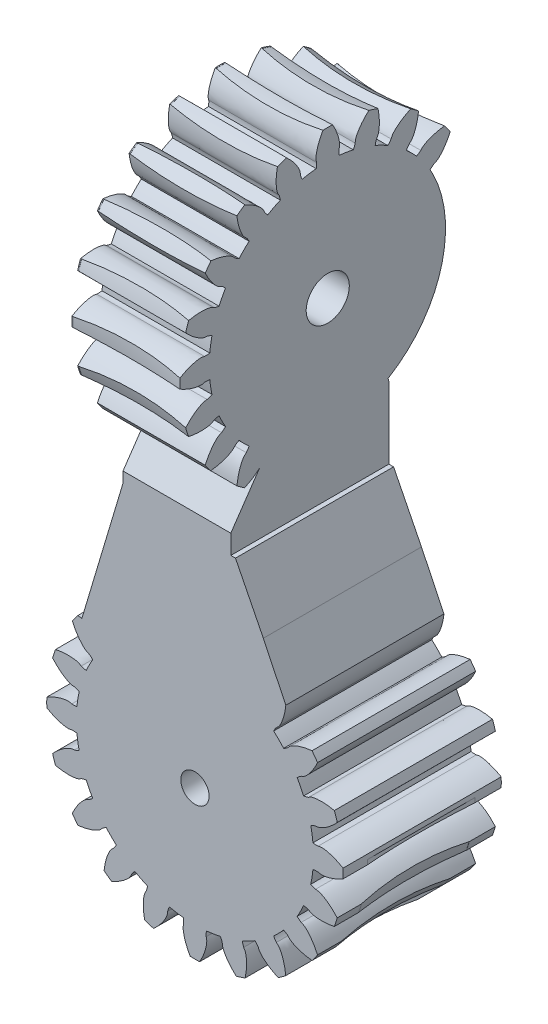
SolidWorks part; units mm, degrees
ref_plane "Спереди" through (0, 0, 0) normal (0, 0, 1) x (1, 0, 0)
ref_plane "Сверху" through (0, 0, 0) normal (0, 1, 0) x (1, 0, 0)
ref_plane "Справа" through (0, 0, 0) normal (1, 0, 0) x (0, 0, -1)
sketch "Sketch1" plane through (0, 0, 0) normal (0, 1, 0) x (1, 0, 0)
  line L1 (0, 0) -> (39.7576, 0)
  line L2 (0, 0) -> (0, 13.7359)
  line L3 (0, 13.7359) -> (39.7576, 13.7359)
  line L4 (39.7576, 0) -> (39.7576, 13.7359)
extrude "Boss-Extrude1" add sketch "Sketch1" along normal blind 49
sketch "Sketch2" plane through (0, 0, 0) normal (0, 0, 1) x (1, 0, 0)
  circle A0 centre (21.6386, 13.5388) radius 1.05
  dimension "D1" = 2.1
extrude "Cut-Extrude1" cut sketch "Sketch2" against normal blind 20
sketch "Sketch3" plane through (0, 0, 0) normal (0, 0, 1) x (1, 0, 0)
  line L0 (0, 49) -> (0, 0) construction
  line L1 (0, 49) -> (16.2999, 49)
  line L2 (0, 49) -> (0, 30.465)
  line L3 (0, 30.465) -> (16.2999, 30.465)
  line L4 (16.2999, 49) -> (16.2999, 30.465)
  line L5 (39.7576, 49) -> (39.7576, 0) construction
  line L6 (39.7576, 49) -> (24.2999, 49)
  line L7 (39.7576, 49) -> (39.7576, 29.8211)
  line L8 (39.7576, 29.8211) -> (24.2999, 29.8211)
  line L9 (24.2999, 49) -> (24.2999, 29.8211)
  dimension "D1" = 8
extrude "Cut-Extrude2" cut sketch "Sketch3" against normal blind 20
sketch "Sketch4" plane through (24.2999, 0, 0) normal (1, 0, 0) x (0, 0, -1)
  circle A0 centre (9.1973, 42.7526) radius 1.6
  dimension "D1" = 3.2
extrude "Cut-Extrude3" cut sketch "Sketch4" against normal blind 10
sketch "Sketch5" plane through (0, 0, 0) normal (0, 0, 1) x (1, 0, 0)
  line L0 (30.5736, 18.0296) -> (24.6471, 29.8211)
  line L1 (43.1167, 38.1094) -> (43.1167, -6.2044)
  line L2 (43.1167, -6.2044) -> (-5.9864, -7.089)
  line L3 (-5.9864, -7.089) -> (-3.1631, 36.0058)
  line L4 (16.2999, 30.465) -> (12.3499, 17.2429)
  line L5 (24.2999, 29.8211) -> (39.7576, 29.8211) construction
  line L6 (24.6471, 29.8211) -> (43.1167, 38.1094)
  line L7 (16.2999, 30.465) -> (-3.1631, 36.0058)
  circle A0 centre (21.6386, 13.5388) radius 10
  line M4 (16.2999, 30.465) -> (0, 30.465)
  line M5 (0, 30.465) -> (0, 0)
  line M6 (0, 0) -> (39.7576, 0)
  line M7 (39.7576, 0) -> (39.7576, 29.8211)
  line M8 (39.7576, 29.8211) -> (24.2999, 29.8211)
  dimension "D1" = 20
extrude "Cut-Extrude4" cut sketch "Sketch5" against normal blind 23 contours A0 L7 M4 M5 M6 M7 M8 region at (28.0579, 24.1503, 0)
sketch "Sketch6" plane through (16.2999, 0, 0) normal (-1, 0, 0) x (0, 0, 1)
  line L0 (-9.1973, 50.2582) -> (3.3847, 50.2582)
  line L1 (3.3847, 50.2582) -> (3.3847, 37.4424)
  line L2 (-5.429, 36.2614) -> (1.4031, 26.2756)
  line L3 (1.4031, 26.2756) -> (3.3847, 37.4424)
  circle A0 centre (-9.1973, 42.7526) radius 7.5056
  line M2 (-13.7359, 30.465) -> (0, 30.465)
  line M3 (0, 30.465) -> (0, 49)
  line M4 (0, 49) -> (-13.7359, 49)
extrude "Cut-Extrude5" cut sketch "Sketch6" against normal blind 28 and the other way blind 10 contours A0 L2 L3 L1 L0 M4 M3 M2 | A0 L2 M2 M3 M4 region at (16.2999, 40.6436, 1.0177) region at (16.2999, 39.3835, -1.6823)
sketch "Sketch7" plane through (16.2999, 0, 0) normal (-1, 0, 0) x (0, 0, 1)
  circle A0 centre (-9.1973, 42.7545) radius 3
  arc A1 (-8.3632, 51.8961) -> (-8.3414, 51.5128) centre (-6.7958, 51.7931) ccw
  arc A2 (-8.8499, 53.749) -> (-9.5447, 53.749) centre (-9.1973, 42.7564) ccw
  arc A3 (-10.0532, 51.5128) -> (-10.0313, 51.8961) centre (-11.5987, 51.7931) ccw
  arc A4 (-10.0532, 51.5128) -> (-11.0898, 51.3486) centre (-9.1973, 42.7545) ccw
  arc A5 (-11.229, 51.7064) -> (-11.0898, 51.3486) centre (-9.7064, 52.0928) ccw
  arc A6 (-12.2644, 53.3182) -> (-12.9252, 53.1036) centre (-9.1973, 42.7545) ccw
  arc A7 (-12.7177, 50.8196) -> (-12.8154, 51.1909) centre (-14.2743, 50.6086) ccw
  arc A8 (-12.7177, 50.8196) -> (-13.6529, 50.3432) centre (-9.1973, 42.7545) ccw
  arc A9 (-13.8958, 50.6404) -> (-13.6529, 50.3432) centre (-12.5672, 51.4784) ccw
  arc A10 (-15.3787, 51.8534) -> (-15.9407, 51.4451) centre (-9.1973, 42.7545) ccw
  arc A11 (-15.0377, 49.337) -> (-15.2453, 49.6599) centre (-16.4528, 48.6553) ccw
  arc A12 (-15.0377, 49.337) -> (-15.7798, 48.5949) centre (-9.1973, 42.7545) ccw
  arc A13 (-16.1027, 48.8025) -> (-15.7798, 48.5949) centre (-15.0981, 50.0101) ccw
  arc A14 (-17.8878, 49.4979) -> (-18.2962, 48.9359) centre (-9.1973, 42.7545) ccw
  arc A15 (-16.786, 47.2101) -> (-17.0832, 47.453) centre (-17.9212, 46.1244) ccw
  arc A16 (-16.786, 47.2101) -> (-17.2624, 46.2749) centre (-9.1973, 42.7545) ccw
  arc A17 (-17.6337, 46.3726) -> (-17.2624, 46.2749) centre (-17.0514, 47.8315) ccw
  arc A18 (-19.5463, 46.4824) -> (-19.761, 45.8216) centre (-9.1973, 42.7545) ccw
  arc A19 (-17.7914, 44.647) -> (-18.1492, 44.7862) centre (-18.5356, 43.2637) ccw
  arc A20 (-17.7914, 44.647) -> (-17.9556, 43.6104) centre (-9.1973, 42.7545) ccw
  arc A21 (-18.3389, 43.5885) -> (-17.9556, 43.6104) centre (-18.2359, 45.156) ccw
  arc A22 (-20.1918, 43.1019) -> (-20.1918, 42.4071) centre (-9.1973, 42.7545) ccw
  arc A23 (-17.9556, 41.8986) -> (-18.3389, 41.9205) centre (-18.2359, 40.353) ccw
  arc A24 (-17.9556, 41.8986) -> (-17.7914, 40.862) centre (-9.1973, 42.7545) ccw
  arc A25 (-18.1492, 40.7228) -> (-17.7914, 40.862) centre (-18.5356, 42.2453) ccw
  arc A26 (-19.761, 39.6874) -> (-19.5463, 39.0266) centre (-9.1973, 42.7545) ccw
  arc A27 (-17.2624, 39.2341) -> (-17.6337, 39.1364) centre (-17.0514, 37.6775) ccw
  arc A28 (-17.2624, 39.2341) -> (-16.786, 38.2989) centre (-9.1973, 42.7545) ccw
  arc A29 (-17.0832, 38.056) -> (-16.786, 38.2989) centre (-17.9212, 39.3846) ccw
  arc A30 (-18.2962, 36.5731) -> (-17.8878, 36.011) centre (-9.1973, 42.7545) ccw
  arc A31 (-15.7798, 36.9141) -> (-16.1027, 36.7065) centre (-15.0981, 35.4989) ccw
  arc A32 (-15.7798, 36.9141) -> (-15.0377, 36.172) centre (-9.1973, 42.7545) ccw
  arc A33 (-15.2453, 35.849) -> (-15.0377, 36.172) centre (-16.4528, 36.8537) ccw
  arc A34 (-15.9407, 34.0639) -> (-15.3787, 33.6556) centre (-9.1973, 42.7545) ccw
  arc A35 (-13.6529, 35.1658) -> (-13.8958, 34.8686) centre (-12.5672, 34.0306) ccw
  arc A36 (-13.6529, 35.1658) -> (-12.7177, 34.6894) centre (-9.1973, 42.7545) ccw
  arc A37 (-12.8154, 34.3181) -> (-12.7177, 34.6894) centre (-14.2743, 34.9004) ccw
  arc A38 (-12.9252, 32.4054) -> (-12.2644, 32.1907) centre (-9.1973, 42.7545) ccw
  arc A39 (-11.0898, 34.1604) -> (-11.229, 33.8026) centre (-9.7064, 33.4162) ccw
  arc A40 (-11.0898, 34.1604) -> (-10.0532, 33.9962) centre (-9.1973, 42.7545) ccw
  arc A41 (-10.0313, 33.6129) -> (-10.0532, 33.9962) centre (-11.5987, 33.7159) ccw
  arc A42 (-9.5447, 31.76) -> (-8.8499, 31.76) centre (-9.1973, 42.7526) ccw
  arc A43 (-8.3414, 33.9962) -> (-8.3632, 33.6129) centre (-6.7958, 33.7159) ccw
  arc A44 (-8.3414, 33.9962) -> (-7.3048, 34.1604) centre (-9.1973, 42.7545) ccw
  arc A45 (-7.1656, 33.8026) -> (-7.3048, 34.1604) centre (-8.6881, 33.4162) ccw
  arc A46 (-6.1302, 32.1907) -> (-5.4694, 32.4054) centre (-9.1973, 42.7545) ccw
  arc A47 (-5.6768, 34.6894) -> (-5.5792, 34.3181) centre (-4.1203, 34.9004) ccw
  arc A48 (-5.6768, 34.6894) -> (-4.7417, 35.1658) centre (-9.1973, 42.7545) ccw
  arc A49 (-4.4988, 34.8686) -> (-4.7417, 35.1658) centre (-5.8274, 34.0306) ccw
  arc A50 (-3.0159, 33.6556) -> (-2.4538, 34.0639) centre (-9.1973, 42.7545) ccw
  arc A51 (-3.3569, 36.172) -> (-3.1492, 35.849) centre (-1.9417, 36.8537) ccw
  arc A52 (-3.3569, 36.172) -> (-2.6148, 36.9141) centre (-9.1973, 42.7545) ccw
  arc A53 (-2.2918, 36.7065) -> (-2.6148, 36.9141) centre (-3.2965, 35.4989) ccw
  arc A54 (-0.5067, 36.011) -> (-0.0983, 36.5731) centre (-9.1973, 42.7545) ccw
  arc A55 (-1.6086, 38.2989) -> (-1.3114, 38.056) centre (-0.4734, 39.3846) ccw
  arc A56 (-1.6086, 38.2989) -> (-1.1321, 39.2341) centre (-9.1973, 42.7545) ccw
  arc A57 (-0.7609, 39.1364) -> (-1.1321, 39.2341) centre (-1.3432, 37.6775) ccw
  arc A58 (1.1518, 39.0266) -> (1.3665, 39.6874) centre (-9.1973, 42.7545) ccw
  arc A59 (-0.6032, 40.862) -> (-0.2454, 40.7228) centre (0.141, 42.2453) ccw
  arc A60 (-0.6032, 40.862) -> (-0.439, 41.8986) centre (-9.1973, 42.7545) ccw
  arc A61 (-0.0557, 41.9205) -> (-0.439, 41.8986) centre (-0.1587, 40.353) ccw
  arc A62 (1.7972, 42.4071) -> (1.7972, 43.1019) centre (-9.1973, 42.7545) ccw
  arc A63 (-0.439, 43.6104) -> (-0.0557, 43.5885) centre (-0.1587, 45.156) ccw
  arc A64 (-0.439, 43.6104) -> (-0.6032, 44.647) centre (-9.1973, 42.7545) ccw
  arc A65 (-0.2454, 44.7862) -> (-0.6032, 44.647) centre (0.141, 43.2637) ccw
  arc A66 (1.3665, 45.8216) -> (1.1518, 46.4824) centre (-9.1973, 42.7545) ccw
  arc A67 (-1.1321, 46.2749) -> (-0.7609, 46.3726) centre (-1.3432, 47.8315) ccw
  arc A68 (-1.1321, 46.2749) -> (-1.6086, 47.2101) centre (-9.1973, 42.7545) ccw
  arc A69 (-1.3114, 47.453) -> (-1.6086, 47.2101) centre (-0.4734, 46.1244) ccw
  arc A70 (-0.0983, 48.9359) -> (-0.5067, 49.4979) centre (-9.1973, 42.7545) ccw
  arc A71 (-2.6148, 48.5949) -> (-2.2918, 48.8025) centre (-3.2965, 50.0101) ccw
  arc A72 (-2.6148, 48.5949) -> (-3.3569, 49.337) centre (-9.1973, 42.7545) ccw
  arc A73 (-3.1492, 49.6599) -> (-3.3569, 49.337) centre (-1.9417, 48.6553) ccw
  arc A74 (-2.4538, 51.4451) -> (-3.0159, 51.8534) centre (-9.1973, 42.7545) ccw
  arc A75 (-4.7417, 50.3432) -> (-4.4988, 50.6404) centre (-5.8274, 51.4784) ccw
  arc A76 (-4.7417, 50.3432) -> (-5.6768, 50.8196) centre (-9.1973, 42.7545) ccw
  arc A77 (-5.5792, 51.1909) -> (-5.6768, 50.8196) centre (-4.1203, 50.6086) ccw
  arc A78 (-5.4694, 53.1036) -> (-6.1302, 53.3182) centre (-9.1973, 42.7545) ccw
  arc A79 (-7.3048, 51.3486) -> (-7.1656, 51.7064) centre (-8.6881, 52.0928) ccw
  arc A80 (-7.3048, 51.3486) -> (-8.3414, 51.5128) centre (-9.1973, 42.7545) ccw
  spline S0 degree 3 poles (-8.3632, 51.8961) (-8.3353, 51.9983) (-8.3222, 52.0737) (-8.3186, 52.1413) (-8.3185, 52.1775) (-8.321, 52.253) (-8.334, 52.3811) (-8.3676, 52.5694) (-8.4293, 52.8074) (-8.5268, 53.0907) (-8.6488, 53.3717) (-8.7612, 53.5917) (-8.8273, 53.7097) (-8.8499, 53.749) knots -0.544106 -0.544106 -0.544106 -0.544106 -0.367071 -0.332661 -0.285394 -0.214472 0.006914 0.350598 0.831726 1.464429 2.260634 2.903028 3.224225 3.224225 3.224225 3.224225 weights 1 1 1 1 1 1 1 1 1 1 1 1 1 1
  spline S1 degree 3 poles (-9.5447, 53.749) (-9.5673, 53.7097) (-9.6333, 53.5917) (-9.7458, 53.3717) (-9.8677, 53.0907) (-9.9652, 52.8074) (-10.027, 52.5694) (-10.0605, 52.3811) (-10.0736, 52.253) (-10.0761, 52.1775) (-10.076, 52.1413) (-10.0724, 52.0737) (-10.0593, 51.9983) (-10.0313, 51.8961) knots 0 0 0 0 0.321197 0.963591 1.759796 2.3925 2.873627 3.217311 3.438697 3.509619 3.556886 3.591297 3.768331 3.768331 3.768331 3.768331 weights 1 1 1 1 1 1 1 1 1 1 1 1 1 1
  spline S2 degree 3 poles (-11.229, 51.7064) (-11.234, 51.8122) (-11.2448, 51.888) (-11.2623, 51.9534) (-11.2734, 51.9878) (-11.2991, 52.0589) (-11.3511, 52.1767) (-11.4411, 52.3454) (-11.5735, 52.5527) (-11.7537, 52.792) (-11.9566, 53.0215) (-12.1315, 53.196) (-12.2307, 53.2879) (-12.2644, 53.3182) knots -0.544106 -0.544106 -0.544106 -0.544106 -0.367071 -0.332661 -0.285394 -0.214472 0.006914 0.350598 0.831726 1.464429 2.260634 2.903028 3.224225 3.224225 3.224225 3.224225 weights 1 1 1 1 1 1 1 1 1 1 1 1 1 1
  spline S3 degree 3 poles (-12.9252, 53.1036) (-12.9345, 53.0592) (-12.9609, 52.9266) (-12.9998, 52.6826) (-13.029, 52.3777) (-13.0342, 52.0781) (-13.0194, 51.8326) (-12.9931, 51.6432) (-12.9659, 51.5173) (-12.9449, 51.4447) (-12.9337, 51.4103) (-12.9093, 51.3472) (-12.8736, 51.2795) (-12.8154, 51.1909) knots 0 0 0 0 0.321197 0.963591 1.759796 2.3925 2.873627 3.217311 3.438697 3.509619 3.556886 3.591297 3.768331 3.768331 3.768331 3.768331 weights 1 1 1 1 1 1 1 1 1 1 1 1 1 1
  spline S4 degree 3 poles (-13.8958, 50.6404) (-13.9333, 50.7395) (-13.967, 50.8082) (-14.0038, 50.8651) (-14.025, 50.8944) (-14.0714, 50.954) (-14.1573, 51.05) (-14.2951, 51.1826) (-14.485, 51.3389) (-14.7304, 51.5108) (-14.9942, 51.6664) (-15.2145, 51.7783) (-15.3373, 51.8349) (-15.3787, 51.8534) knots -0.544106 -0.544106 -0.544106 -0.544106 -0.367071 -0.332661 -0.285394 -0.214472 0.006914 0.350598 0.831726 1.464429 2.260634 2.903028 3.224225 3.224225 3.224225 3.224225 weights 1 1 1 1 1 1 1 1 1 1 1 1 1 1
  spline S5 degree 3 poles (-15.9407, 51.4451) (-15.9359, 51.4) (-15.92, 51.2657) (-15.8816, 51.0216) (-15.8152, 50.7226) (-15.7275, 50.4361) (-15.6376, 50.2072) (-15.554, 50.0352) (-15.4893, 49.9239) (-15.4469, 49.8613) (-15.4256, 49.8321) (-15.3829, 49.7795) (-15.328, 49.7262) (-15.2453, 49.6599) knots 0 0 0 0 0.321197 0.963591 1.759796 2.3925 2.873627 3.217311 3.438697 3.509619 3.556886 3.591297 3.768331 3.768331 3.768331 3.768331 weights 1 1 1 1 1 1 1 1 1 1 1 1 1 1
  spline S6 degree 3 poles (-16.1027, 48.8025) (-16.169, 48.8852) (-16.2223, 48.9401) (-16.2749, 48.9828) (-16.3041, 49.0041) (-16.3667, 49.0465) (-16.478, 49.1113) (-16.65, 49.1948) (-16.8789, 49.2848) (-17.1654, 49.3724) (-17.4644, 49.4389) (-17.7085, 49.4772) (-17.8428, 49.4932) (-17.8878, 49.4979) knots -0.544106 -0.544106 -0.544106 -0.544106 -0.367071 -0.332661 -0.285394 -0.214472 0.006914 0.350598 0.831726 1.464429 2.260634 2.903028 3.224225 3.224225 3.224225 3.224225 weights 1 1 1 1 1 1 1 1 1 1 1 1 1 1
  spline S7 degree 3 poles (-18.2962, 48.9359) (-18.2777, 48.8945) (-18.2211, 48.7717) (-18.1092, 48.5514) (-17.9536, 48.2876) (-17.7817, 48.0422) (-17.6254, 47.8523) (-17.4928, 47.7145) (-17.3968, 47.6286) (-17.3372, 47.5822) (-17.3079, 47.561) (-17.251, 47.5242) (-17.1823, 47.4905) (-17.0832, 47.453) knots 0 0 0 0 0.321197 0.963591 1.759796 2.3925 2.873627 3.217311 3.438697 3.509619 3.556886 3.591297 3.768331 3.768331 3.768331 3.768331 weights 1 1 1 1 1 1 1 1 1 1 1 1 1 1
  spline S8 degree 3 poles (-17.6337, 46.3726) (-17.7223, 46.4308) (-17.7899, 46.4665) (-17.8531, 46.4909) (-17.8875, 46.5021) (-17.9601, 46.5231) (-18.086, 46.5503) (-18.2754, 46.5766) (-18.5209, 46.5914) (-18.8205, 46.5862) (-19.1254, 46.557) (-19.3693, 46.5181) (-19.502, 46.4917) (-19.5463, 46.4824) knots -0.544106 -0.544106 -0.544106 -0.544106 -0.367071 -0.332661 -0.285394 -0.214472 0.006914 0.350598 0.831726 1.464429 2.260634 2.903028 3.224225 3.224225 3.224225 3.224225 weights 1 1 1 1 1 1 1 1 1 1 1 1 1 1
  spline S9 degree 3 poles (-19.761, 45.8216) (-19.7307, 45.788) (-19.6388, 45.6887) (-19.4643, 45.5138) (-19.2348, 45.3109) (-18.9955, 45.1307) (-18.7882, 44.9984) (-18.6195, 44.9083) (-18.5017, 44.8563) (-18.4306, 44.8306) (-18.3962, 44.8195) (-18.3308, 44.802) (-18.255, 44.7912) (-18.1492, 44.7862) knots 0 0 0 0 0.321197 0.963591 1.759796 2.3925 2.873627 3.217311 3.438697 3.509619 3.556886 3.591297 3.768331 3.768331 3.768331 3.768331 weights 1 1 1 1 1 1 1 1 1 1 1 1 1 1
  spline S10 degree 3 poles (-18.3389, 43.5885) (-18.4411, 43.6165) (-18.5165, 43.6296) (-18.5841, 43.6332) (-18.6203, 43.6333) (-18.6958, 43.6308) (-18.8239, 43.6178) (-19.0122, 43.5842) (-19.2502, 43.5224) (-19.5335, 43.425) (-19.8145, 43.303) (-20.0345, 43.1905) (-20.1525, 43.1245) (-20.1918, 43.1019) knots -0.544106 -0.544106 -0.544106 -0.544106 -0.367071 -0.332661 -0.285394 -0.214472 0.006914 0.350598 0.831726 1.464429 2.260634 2.903028 3.224225 3.224225 3.224225 3.224225 weights 1 1 1 1 1 1 1 1 1 1 1 1 1 1
  spline S11 degree 3 poles (-20.1918, 42.4071) (-20.1525, 42.3845) (-20.0345, 42.3185) (-19.8145, 42.206) (-19.5335, 42.084) (-19.2502, 41.9865) (-19.0122, 41.9248) (-18.8239, 41.8912) (-18.6958, 41.8782) (-18.6203, 41.8757) (-18.5841, 41.8758) (-18.5165, 41.8794) (-18.4411, 41.8925) (-18.3389, 41.9205) knots 0 0 0 0 0.321197 0.963591 1.759796 2.3925 2.873627 3.217311 3.438697 3.509619 3.556886 3.591297 3.768331 3.768331 3.768331 3.768331 weights 1 1 1 1 1 1 1 1 1 1 1 1 1 1
  spline S12 degree 3 poles (-18.1492, 40.7228) (-18.255, 40.7178) (-18.3308, 40.707) (-18.3962, 40.6895) (-18.4306, 40.6784) (-18.5017, 40.6527) (-18.6195, 40.6007) (-18.7882, 40.5106) (-18.9955, 40.3783) (-19.2348, 40.1981) (-19.4643, 39.9952) (-19.6388, 39.8203) (-19.7307, 39.721) (-19.761, 39.6874) knots -0.544106 -0.544106 -0.544106 -0.544106 -0.367071 -0.332661 -0.285394 -0.214472 0.006914 0.350598 0.831726 1.464429 2.260634 2.903028 3.224225 3.224225 3.224225 3.224225 weights 1 1 1 1 1 1 1 1 1 1 1 1 1 1
  spline S13 degree 3 poles (-19.5463, 39.0266) (-19.502, 39.0172) (-19.3693, 38.9909) (-19.1254, 38.952) (-18.8205, 38.9228) (-18.5209, 38.9176) (-18.2754, 38.9324) (-18.086, 38.9587) (-17.9601, 38.9859) (-17.8875, 39.0069) (-17.8531, 39.0181) (-17.7899, 39.0425) (-17.7223, 39.0782) (-17.6337, 39.1364) knots 0 0 0 0 0.321197 0.963591 1.759796 2.3925 2.873627 3.217311 3.438697 3.509619 3.556886 3.591297 3.768331 3.768331 3.768331 3.768331 weights 1 1 1 1 1 1 1 1 1 1 1 1 1 1
  spline S14 degree 3 poles (-17.0832, 38.056) (-17.1823, 38.0185) (-17.251, 37.9848) (-17.3079, 37.948) (-17.3372, 37.9268) (-17.3968, 37.8804) (-17.4928, 37.7945) (-17.6254, 37.6567) (-17.7817, 37.4668) (-17.9536, 37.2214) (-18.1092, 36.9576) (-18.2211, 36.7373) (-18.2777, 36.6145) (-18.2962, 36.5731) knots -0.544106 -0.544106 -0.544106 -0.544106 -0.367071 -0.332661 -0.285394 -0.214472 0.006914 0.350598 0.831726 1.464429 2.260634 2.903028 3.224225 3.224225 3.224225 3.224225 weights 1 1 1 1 1 1 1 1 1 1 1 1 1 1
  spline S15 degree 3 poles (-17.8878, 36.011) (-17.8428, 36.0158) (-17.7085, 36.0318) (-17.4644, 36.0701) (-17.1654, 36.1366) (-16.8789, 36.2242) (-16.65, 36.3142) (-16.478, 36.3977) (-16.3667, 36.4625) (-16.3041, 36.5049) (-16.2749, 36.5262) (-16.2223, 36.5689) (-16.169, 36.6238) (-16.1027, 36.7065) knots 0 0 0 0 0.321197 0.963591 1.759796 2.3925 2.873627 3.217311 3.438697 3.509619 3.556886 3.591297 3.768331 3.768331 3.768331 3.768331 weights 1 1 1 1 1 1 1 1 1 1 1 1 1 1
  spline S16 degree 3 poles (-15.2453, 35.849) (-15.328, 35.7828) (-15.3829, 35.7295) (-15.4256, 35.6769) (-15.4469, 35.6477) (-15.4893, 35.5851) (-15.554, 35.4738) (-15.6376, 35.3018) (-15.7275, 35.0729) (-15.8152, 34.7864) (-15.8816, 34.4874) (-15.92, 34.2433) (-15.9359, 34.109) (-15.9407, 34.0639) knots -0.544106 -0.544106 -0.544106 -0.544106 -0.367071 -0.332661 -0.285394 -0.214472 0.006914 0.350598 0.831726 1.464429 2.260634 2.903028 3.224225 3.224225 3.224225 3.224225 weights 1 1 1 1 1 1 1 1 1 1 1 1 1 1
  spline S17 degree 3 poles (-15.3787, 33.6556) (-15.3373, 33.674) (-15.2145, 33.7307) (-14.9942, 33.8426) (-14.7304, 33.9982) (-14.485, 34.1701) (-14.2951, 34.3264) (-14.1573, 34.459) (-14.0714, 34.555) (-14.025, 34.6146) (-14.0038, 34.6439) (-13.967, 34.7008) (-13.9333, 34.7695) (-13.8958, 34.8686) knots 0 0 0 0 0.321197 0.963591 1.759796 2.3925 2.873627 3.217311 3.438697 3.509619 3.556886 3.591297 3.768331 3.768331 3.768331 3.768331 weights 1 1 1 1 1 1 1 1 1 1 1 1 1 1
  spline S18 degree 3 poles (-12.8154, 34.3181) (-12.8736, 34.2295) (-12.9093, 34.1618) (-12.9337, 34.0987) (-12.9449, 34.0643) (-12.9659, 33.9917) (-12.9931, 33.8658) (-13.0194, 33.6764) (-13.0342, 33.4309) (-13.029, 33.1313) (-12.9998, 32.8264) (-12.9609, 32.5824) (-12.9345, 32.4498) (-12.9252, 32.4054) knots -0.544106 -0.544106 -0.544106 -0.544106 -0.367071 -0.332661 -0.285394 -0.214472 0.006914 0.350598 0.831726 1.464429 2.260634 2.903028 3.224225 3.224225 3.224225 3.224225 weights 1 1 1 1 1 1 1 1 1 1 1 1 1 1
  spline S19 degree 3 poles (-12.2644, 32.1907) (-12.2307, 32.2211) (-12.1315, 32.3129) (-11.9566, 32.4874) (-11.7537, 32.717) (-11.5735, 32.9563) (-11.4411, 33.1636) (-11.3511, 33.3323) (-11.2991, 33.4501) (-11.2734, 33.5212) (-11.2623, 33.5556) (-11.2448, 33.621) (-11.234, 33.6968) (-11.229, 33.8026) knots 0 0 0 0 0.321197 0.963591 1.759796 2.3925 2.873627 3.217311 3.438697 3.509619 3.556886 3.591297 3.768331 3.768331 3.768331 3.768331 weights 1 1 1 1 1 1 1 1 1 1 1 1 1 1
  spline S20 degree 3 poles (-10.0313, 33.6129) (-10.0593, 33.5107) (-10.0724, 33.4353) (-10.076, 33.3677) (-10.0761, 33.3315) (-10.0736, 33.256) (-10.0605, 33.1279) (-10.027, 32.9396) (-9.9652, 32.7016) (-9.8677, 32.4183) (-9.7458, 32.1373) (-9.6333, 31.9173) (-9.5673, 31.7993) (-9.5447, 31.76) knots -0.544106 -0.544106 -0.544106 -0.544106 -0.367071 -0.332661 -0.285394 -0.214472 0.006914 0.350598 0.831726 1.464429 2.260634 2.903028 3.224225 3.224225 3.224225 3.224225 weights 1 1 1 1 1 1 1 1 1 1 1 1 1 1
  spline S21 degree 3 poles (-8.8499, 31.76) (-8.8273, 31.7993) (-8.7612, 31.9173) (-8.6488, 32.1373) (-8.5268, 32.4183) (-8.4293, 32.7016) (-8.3676, 32.9396) (-8.334, 33.1279) (-8.321, 33.256) (-8.3185, 33.3315) (-8.3186, 33.3677) (-8.3222, 33.4353) (-8.3353, 33.5107) (-8.3632, 33.6129) knots 0 0 0 0 0.321197 0.963591 1.759796 2.3925 2.873627 3.217311 3.438697 3.509619 3.556886 3.591297 3.768331 3.768331 3.768331 3.768331 weights 1 1 1 1 1 1 1 1 1 1 1 1 1 1
  spline S22 degree 3 poles (-7.1656, 33.8026) (-7.1606, 33.6968) (-7.1497, 33.621) (-7.1323, 33.5556) (-7.1212, 33.5212) (-7.0955, 33.4501) (-7.0435, 33.3323) (-6.9534, 33.1636) (-6.8211, 32.9563) (-6.6409, 32.717) (-6.438, 32.4874) (-6.2631, 32.3129) (-6.1638, 32.2211) (-6.1302, 32.1907) knots -0.544106 -0.544106 -0.544106 -0.544106 -0.367071 -0.332661 -0.285394 -0.214472 0.006914 0.350598 0.831726 1.464429 2.260634 2.903028 3.224225 3.224225 3.224225 3.224225 weights 1 1 1 1 1 1 1 1 1 1 1 1 1 1
  spline S23 degree 3 poles (-5.4694, 32.4054) (-5.46, 32.4498) (-5.4337, 32.5824) (-5.3948, 32.8264) (-5.3656, 33.1313) (-5.3604, 33.4309) (-5.3752, 33.6764) (-5.4015, 33.8658) (-5.4287, 33.9917) (-5.4497, 34.0643) (-5.4609, 34.0987) (-5.4852, 34.1618) (-5.521, 34.2295) (-5.5792, 34.3181) knots 0 0 0 0 0.321197 0.963591 1.759796 2.3925 2.873627 3.217311 3.438697 3.509619 3.556886 3.591297 3.768331 3.768331 3.768331 3.768331 weights 1 1 1 1 1 1 1 1 1 1 1 1 1 1
  spline S24 degree 3 poles (-4.4988, 34.8686) (-4.4613, 34.7695) (-4.4276, 34.7008) (-4.3907, 34.6439) (-4.3695, 34.6146) (-4.3231, 34.555) (-4.2373, 34.459) (-4.0995, 34.3264) (-3.9096, 34.1701) (-3.6642, 33.9982) (-3.4004, 33.8426) (-3.1801, 33.7307) (-3.0573, 33.674) (-3.0159, 33.6556) knots -0.544106 -0.544106 -0.544106 -0.544106 -0.367071 -0.332661 -0.285394 -0.214472 0.006914 0.350598 0.831726 1.464429 2.260634 2.903028 3.224225 3.224225 3.224225 3.224225 weights 1 1 1 1 1 1 1 1 1 1 1 1 1 1
  spline S25 degree 3 poles (-2.4538, 34.0639) (-2.4586, 34.109) (-2.4746, 34.2433) (-2.5129, 34.4874) (-2.5794, 34.7864) (-2.667, 35.0729) (-2.757, 35.3018) (-2.8405, 35.4738) (-2.9053, 35.5851) (-2.9477, 35.6477) (-2.969, 35.6769) (-3.0116, 35.7295) (-3.0666, 35.7828) (-3.1492, 35.849) knots 0 0 0 0 0.321197 0.963591 1.759796 2.3925 2.873627 3.217311 3.438697 3.509619 3.556886 3.591297 3.768331 3.768331 3.768331 3.768331 weights 1 1 1 1 1 1 1 1 1 1 1 1 1 1
  spline S26 degree 3 poles (-2.2918, 36.7065) (-2.2256, 36.6238) (-2.1723, 36.5689) (-2.1197, 36.5262) (-2.0905, 36.5049) (-2.0279, 36.4625) (-1.9166, 36.3977) (-1.7446, 36.3142) (-1.5157, 36.2242) (-1.2292, 36.1366) (-0.9302, 36.0701) (-0.6861, 36.0318) (-0.5518, 36.0158) (-0.5067, 36.011) knots -0.544106 -0.544106 -0.544106 -0.544106 -0.367071 -0.332661 -0.285394 -0.214472 0.006914 0.350598 0.831726 1.464429 2.260634 2.903028 3.224225 3.224225 3.224225 3.224225 weights 1 1 1 1 1 1 1 1 1 1 1 1 1 1
  spline S27 degree 3 poles (-0.0983, 36.5731) (-0.1168, 36.6145) (-0.1735, 36.7373) (-0.2854, 36.9576) (-0.441, 37.2214) (-0.6129, 37.4668) (-0.7692, 37.6567) (-0.9018, 37.7945) (-0.9978, 37.8804) (-1.0574, 37.9268) (-1.0867, 37.948) (-1.1435, 37.9848) (-1.2123, 38.0185) (-1.3114, 38.056) knots 0 0 0 0 0.321197 0.963591 1.759796 2.3925 2.873627 3.217311 3.438697 3.509619 3.556886 3.591297 3.768331 3.768331 3.768331 3.768331 weights 1 1 1 1 1 1 1 1 1 1 1 1 1 1
  spline S28 degree 3 poles (-0.7609, 39.1364) (-0.6723, 39.0782) (-0.6046, 39.0425) (-0.5414, 39.0181) (-0.5071, 39.0069) (-0.4345, 38.9859) (-0.3086, 38.9587) (-0.1192, 38.9324) (0.1263, 38.9176) (0.4259, 38.9228) (0.7308, 38.952) (0.9748, 38.9909) (1.1074, 39.0172) (1.1518, 39.0266) knots -0.544106 -0.544106 -0.544106 -0.544106 -0.367071 -0.332661 -0.285394 -0.214472 0.006914 0.350598 0.831726 1.464429 2.260634 2.903028 3.224225 3.224225 3.224225 3.224225 weights 1 1 1 1 1 1 1 1 1 1 1 1 1 1
  spline S29 degree 3 poles (1.3665, 39.6874) (1.3361, 39.721) (1.2443, 39.8203) (1.0698, 39.9952) (0.8403, 40.1981) (0.6009, 40.3783) (0.3936, 40.5106) (0.2249, 40.6007) (0.1071, 40.6527) (0.0361, 40.6784) (0.0016, 40.6895) (-0.0638, 40.707) (-0.1396, 40.7178) (-0.2454, 40.7228) knots 0 0 0 0 0.321197 0.963591 1.759796 2.3925 2.873627 3.217311 3.438697 3.509619 3.556886 3.591297 3.768331 3.768331 3.768331 3.768331 weights 1 1 1 1 1 1 1 1 1 1 1 1 1 1
  spline S30 degree 3 poles (-0.0557, 41.9205) (0.0465, 41.8925) (0.1219, 41.8794) (0.1895, 41.8758) (0.2257, 41.8757) (0.3012, 41.8782) (0.4293, 41.8912) (0.6176, 41.9248) (0.8557, 41.9865) (1.139, 42.084) (1.4199, 42.206) (1.6399, 42.3185) (1.7579, 42.3845) (1.7972, 42.4071) knots -0.544106 -0.544106 -0.544106 -0.544106 -0.367071 -0.332661 -0.285394 -0.214472 0.006914 0.350598 0.831726 1.464429 2.260634 2.903028 3.224225 3.224225 3.224225 3.224225 weights 1 1 1 1 1 1 1 1 1 1 1 1 1 1
  spline S31 degree 3 poles (1.7972, 43.1019) (1.7579, 43.1245) (1.6399, 43.1905) (1.4199, 43.303) (1.139, 43.425) (0.8557, 43.5224) (0.6176, 43.5842) (0.4293, 43.6178) (0.3012, 43.6308) (0.2257, 43.6333) (0.1895, 43.6332) (0.1219, 43.6296) (0.0465, 43.6165) (-0.0557, 43.5885) knots 0 0 0 0 0.321197 0.963591 1.759796 2.3925 2.873627 3.217311 3.438697 3.509619 3.556886 3.591297 3.768331 3.768331 3.768331 3.768331 weights 1 1 1 1 1 1 1 1 1 1 1 1 1 1
  spline S32 degree 3 poles (-0.2454, 44.7862) (-0.1396, 44.7912) (-0.0638, 44.802) (0.0016, 44.8195) (0.0361, 44.8306) (0.1071, 44.8563) (0.2249, 44.9083) (0.3936, 44.9984) (0.6009, 45.1307) (0.8403, 45.3109) (1.0698, 45.5138) (1.2443, 45.6887) (1.3361, 45.788) (1.3665, 45.8216) knots -0.544106 -0.544106 -0.544106 -0.544106 -0.367071 -0.332661 -0.285394 -0.214472 0.006914 0.350598 0.831726 1.464429 2.260634 2.903028 3.224225 3.224225 3.224225 3.224225 weights 1 1 1 1 1 1 1 1 1 1 1 1 1 1
  spline S33 degree 3 poles (1.1518, 46.4824) (1.1074, 46.4917) (0.9748, 46.5181) (0.7308, 46.557) (0.4259, 46.5862) (0.1263, 46.5914) (-0.1192, 46.5766) (-0.3086, 46.5503) (-0.4345, 46.5231) (-0.5071, 46.5021) (-0.5414, 46.4909) (-0.6046, 46.4665) (-0.6723, 46.4308) (-0.7609, 46.3726) knots 0 0 0 0 0.321197 0.963591 1.759796 2.3925 2.873627 3.217311 3.438697 3.509619 3.556886 3.591297 3.768331 3.768331 3.768331 3.768331 weights 1 1 1 1 1 1 1 1 1 1 1 1 1 1
  spline S34 degree 3 poles (-1.3114, 47.453) (-1.2123, 47.4905) (-1.1435, 47.5242) (-1.0867, 47.561) (-1.0574, 47.5822) (-0.9978, 47.6286) (-0.9018, 47.7145) (-0.7692, 47.8523) (-0.6129, 48.0422) (-0.441, 48.2876) (-0.2854, 48.5514) (-0.1735, 48.7717) (-0.1168, 48.8945) (-0.0983, 48.9359) knots -0.544106 -0.544106 -0.544106 -0.544106 -0.367071 -0.332661 -0.285394 -0.214472 0.006914 0.350598 0.831726 1.464429 2.260634 2.903028 3.224225 3.224225 3.224225 3.224225 weights 1 1 1 1 1 1 1 1 1 1 1 1 1 1
  spline S35 degree 3 poles (-0.5067, 49.4979) (-0.5518, 49.4932) (-0.6861, 49.4772) (-0.9302, 49.4389) (-1.2292, 49.3724) (-1.5157, 49.2848) (-1.7446, 49.1948) (-1.9166, 49.1113) (-2.0279, 49.0465) (-2.0905, 49.0041) (-2.1197, 48.9828) (-2.1723, 48.9401) (-2.2256, 48.8852) (-2.2918, 48.8025) knots 0 0 0 0 0.321197 0.963591 1.759796 2.3925 2.873627 3.217311 3.438697 3.509619 3.556886 3.591297 3.768331 3.768331 3.768331 3.768331 weights 1 1 1 1 1 1 1 1 1 1 1 1 1 1
  spline S36 degree 3 poles (-3.1492, 49.6599) (-3.0666, 49.7262) (-3.0116, 49.7795) (-2.969, 49.8321) (-2.9477, 49.8613) (-2.9053, 49.9239) (-2.8405, 50.0352) (-2.757, 50.2072) (-2.667, 50.4361) (-2.5794, 50.7226) (-2.5129, 51.0216) (-2.4746, 51.2657) (-2.4586, 51.4) (-2.4538, 51.4451) knots -0.544106 -0.544106 -0.544106 -0.544106 -0.367071 -0.332661 -0.285394 -0.214472 0.006914 0.350598 0.831726 1.464429 2.260634 2.903028 3.224225 3.224225 3.224225 3.224225 weights 1 1 1 1 1 1 1 1 1 1 1 1 1 1
  spline S37 degree 3 poles (-3.0159, 51.8534) (-3.0573, 51.8349) (-3.1801, 51.7783) (-3.4004, 51.6664) (-3.6642, 51.5108) (-3.9096, 51.3389) (-4.0995, 51.1826) (-4.2373, 51.05) (-4.3231, 50.954) (-4.3695, 50.8944) (-4.3907, 50.8651) (-4.4276, 50.8082) (-4.4613, 50.7395) (-4.4988, 50.6404) knots 0 0 0 0 0.321197 0.963591 1.759796 2.3925 2.873627 3.217311 3.438697 3.509619 3.556886 3.591297 3.768331 3.768331 3.768331 3.768331 weights 1 1 1 1 1 1 1 1 1 1 1 1 1 1
  spline S38 degree 3 poles (-5.5792, 51.1909) (-5.521, 51.2795) (-5.4852, 51.3472) (-5.4609, 51.4103) (-5.4497, 51.4447) (-5.4287, 51.5173) (-5.4015, 51.6432) (-5.3752, 51.8326) (-5.3604, 52.0781) (-5.3656, 52.3777) (-5.3948, 52.6826) (-5.4337, 52.9266) (-5.46, 53.0592) (-5.4694, 53.1036) knots -0.544106 -0.544106 -0.544106 -0.544106 -0.367071 -0.332661 -0.285394 -0.214472 0.006914 0.350598 0.831726 1.464429 2.260634 2.903028 3.224225 3.224225 3.224225 3.224225 weights 1 1 1 1 1 1 1 1 1 1 1 1 1 1
  spline S39 degree 3 poles (-6.1302, 53.3182) (-6.1638, 53.2879) (-6.2631, 53.196) (-6.438, 53.0215) (-6.6409, 52.792) (-6.8211, 52.5527) (-6.9534, 52.3454) (-7.0435, 52.1767) (-7.0955, 52.0589) (-7.1212, 51.9878) (-7.1323, 51.9534) (-7.1497, 51.888) (-7.1606, 51.8122) (-7.1656, 51.7064) knots 0 0 0 0 0.321197 0.963591 1.759796 2.3925 2.873627 3.217311 3.438697 3.509619 3.556886 3.591297 3.768331 3.768331 3.768331 3.768331 weights 1 1 1 1 1 1 1 1 1 1 1 1 1 1
extrude "Boss-Extrude2" add sketch "Sketch7" against normal up to surface (8 mm away) up to face at (24.2999, 42.7526, -10.7973)
ref_plane "Plane1" through (0, 0, -9.1973) normal (0, 0, -1) x (-1, 0, 0)
sketch "Sketch9" plane through (0, 0, -9.1973) normal (0, 0, -1) x (-1, 0, 0)
  line L0 (-20.3735, 42.7526) -> (-14.496, 42.7526) construction
  line L1 (-24.3735, 53.7471) -> (-24.3735, 54.7379)
  line L2 (-24.3735, 54.7379) -> (-16.3735, 54.7379)
  line L3 (-16.3735, 54.7379) -> (-16.3735, 53.7471)
  spline S0 degree 3 poles (-16.3735, 53.7471) (-17.7069, 53.5421) (-20.3735, 53.3386) (-23.0402, 53.5421) (-24.3735, 53.7471) knots 0 0 0 0 0.5 1 1 1 1
revolve "Cut-Revolve1" cut sketch "Sketch9" angle 90 about L0 other way angle 120
sketch "Sketch10" plane through (16.2999, 0, 0) normal (-1, 0, 0) x (0, 0, 1)
  line L0 (-17.0381, 46.7496) -> (-22.5155, 49.1781)
  line L1 (-22.5155, 49.1781) -> (-21.1078, 31.6437)
  line L2 (-21.1078, 31.6437) -> (-14.3398, 32.9553)
  line L3 (-14.3398, 32.9553) -> (-13.6735, 35.3626)
  arc A0 (-17.0381, 46.7496) -> (-13.6735, 35.3626) centre (-9.1743, 42.8827) ccw
  arc A1 (-16.786, 47.2101) -> (-17.2624, 46.2749) centre (-9.1973, 42.7545) ccw construction
extrude "Cut-Extrude6" cut sketch "Sketch10" against normal blind 9
sketch "Sketch11" plane through (0, 0, 0) normal (0, 0, 1) x (1, 0, 0)
  line L0 (26.7156, 25.7055) -> (28.3821, 22.2313)
  line L1 (14.7332, 25.2204) -> (12.948, 20.2842)
  line L2 (15.661, 28.3264) -> (12.3499, 17.2429) construction
  line L3 (30.5736, 18.0296) -> (25.3983, 28.3264) construction
  circle A0 centre (21.6386, 13.5388) radius 1.75
  arc A1 (20.7827, 22.2991) -> (20.8048, 22.6781) centre (19.2371, 22.5794) ccw
  arc A2 (20.7827, 22.2991) -> (19.7461, 22.1349) centre (21.6386, 13.5408) ccw
  arc A3 (19.6069, 22.4927) -> (19.7461, 22.1349) centre (21.1295, 22.8791) ccw
  arc A4 (18.5715, 24.1045) -> (17.9107, 23.8898) centre (21.6386, 13.5408) ccw
  arc A5 (18.1182, 21.6059) -> (18.0205, 21.9772) centre (16.5616, 21.3949) ccw
  arc A6 (18.1182, 21.6059) -> (17.183, 21.1294) centre (21.6386, 13.5408) ccw
  arc A7 (16.9401, 21.4267) -> (17.183, 21.1294) centre (18.2687, 22.2647) ccw
  arc A8 (15.4572, 22.6397) -> (14.8952, 22.2313) centre (21.6386, 13.5408) ccw
  arc A9 (15.7982, 20.1233) -> (15.5906, 20.4462) centre (14.383, 19.4416) ccw
  arc A10 (15.7982, 20.1233) -> (15.0561, 19.3812) centre (21.6386, 13.5408) ccw
  arc A11 (14.7332, 19.5888) -> (15.0561, 19.3812) centre (15.7378, 20.7963) ccw
  arc A12 (12.948, 20.2842) -> (12.5397, 19.7222) centre (21.6386, 13.5408) ccw
  arc A13 (14.0499, 17.9964) -> (13.7527, 18.2393) centre (12.9147, 16.9107) ccw
  arc A14 (14.0499, 17.9964) -> (13.5735, 17.0612) centre (21.6386, 13.5408) ccw
  arc A15 (13.2022, 17.1589) -> (13.5735, 17.0612) centre (13.7845, 18.6178) ccw
  arc A16 (11.2895, 17.2686) -> (11.0749, 16.6079) centre (21.6386, 13.5408) ccw
  arc A17 (13.0445, 15.4333) -> (12.6867, 15.5725) centre (12.3003, 14.0499) ccw
  arc A18 (13.0445, 15.4333) -> (12.8803, 14.3966) centre (21.6386, 13.5408) ccw
  arc A19 (12.497, 14.3748) -> (12.8803, 14.3966) centre (12.6, 15.9422) ccw
  arc A20 (10.6441, 13.8882) -> (10.6441, 13.1934) centre (21.6386, 13.5408) ccw
  arc A21 (12.8803, 12.6849) -> (12.497, 12.7067) centre (12.6, 11.1393) ccw
  arc A22 (12.8803, 12.6849) -> (13.0445, 11.6483) centre (21.6386, 13.5408) ccw
  arc A23 (12.6867, 11.5091) -> (13.0445, 11.6483) centre (12.3003, 13.0316) ccw
  arc A24 (11.0749, 10.4737) -> (11.2895, 9.8129) centre (21.6386, 13.5408) ccw
  arc A25 (13.5735, 10.0203) -> (13.2022, 9.9227) centre (13.7845, 8.4638) ccw
  arc A26 (13.5735, 10.0203) -> (14.0499, 9.0852) centre (21.6386, 13.5408) ccw
  arc A27 (13.7527, 8.8422) -> (14.0499, 9.0852) centre (12.9147, 10.1709) ccw
  arc A28 (12.5397, 7.3594) -> (12.948, 6.7973) centre (21.6386, 13.5408) ccw
  arc A29 (15.0561, 7.7004) -> (14.7332, 7.4927) centre (15.7378, 6.2852) ccw
  arc A30 (15.0561, 7.7004) -> (15.7982, 6.9582) centre (21.6386, 13.5408) ccw
  arc A31 (15.5906, 6.6353) -> (15.7982, 6.9582) centre (14.383, 7.64) ccw
  arc A32 (14.8952, 4.8502) -> (15.4572, 4.4418) centre (21.6386, 13.5408) ccw
  arc A33 (17.183, 5.9521) -> (16.9401, 5.6549) centre (18.2687, 4.8169) ccw
  arc A34 (17.183, 5.9521) -> (18.1182, 5.4756) centre (21.6386, 13.5408) ccw
  arc A35 (18.0205, 5.1044) -> (18.1182, 5.4756) centre (16.5616, 5.6867) ccw
  arc A36 (17.9107, 3.1917) -> (18.5715, 2.977) centre (21.6386, 13.5408) ccw
  arc A37 (19.7461, 4.9467) -> (19.6069, 4.5889) centre (21.1295, 4.2025) ccw
  arc A38 (19.7461, 4.9467) -> (20.7827, 4.7825) centre (21.6386, 13.5408) ccw
  arc A39 (20.8046, 4.3992) -> (20.7827, 4.7825) centre (19.2371, 4.5022) ccw
  arc A40 (21.2912, 2.5463) -> (21.986, 2.5463) centre (21.6386, 13.5388) ccw
  arc A41 (22.4945, 4.7825) -> (22.4726, 4.3992) centre (24.0401, 4.5022) ccw
  arc A42 (22.4945, 4.7825) -> (23.5311, 4.9467) centre (21.6386, 13.5408) ccw
  arc A43 (23.6703, 4.5889) -> (23.5311, 4.9467) centre (22.1478, 4.2025) ccw
  arc A44 (24.7057, 2.977) -> (25.3665, 3.1917) centre (21.6386, 13.5408) ccw
  arc A45 (25.159, 5.4756) -> (25.2567, 5.1044) centre (26.7156, 5.6867) ccw
  arc A46 (25.159, 5.4756) -> (26.0942, 5.9521) centre (21.6386, 13.5408) ccw
  arc A47 (26.3371, 5.6549) -> (26.0942, 5.9521) centre (25.0085, 4.8169) ccw
  arc A48 (27.82, 4.4418) -> (28.3821, 4.8502) centre (21.6386, 13.5408) ccw
  arc A49 (27.479, 6.9582) -> (27.6866, 6.6353) centre (28.8942, 7.64) ccw
  arc A50 (27.479, 6.9582) -> (28.2211, 7.7004) centre (21.6386, 13.5408) ccw
  arc A51 (28.5441, 7.4927) -> (28.2211, 7.7004) centre (27.5394, 6.2852) ccw
  arc A52 (30.3292, 6.7973) -> (30.7375, 7.3594) centre (21.6386, 13.5408) ccw
  arc A53 (29.2273, 9.0852) -> (29.5245, 8.8422) centre (30.3625, 10.1709) ccw
  arc A54 (29.2273, 9.0852) -> (29.7037, 10.0203) centre (21.6386, 13.5408) ccw
  arc A55 (30.075, 9.9227) -> (29.7037, 10.0203) centre (29.4927, 8.4638) ccw
  arc A56 (31.9877, 9.8129) -> (32.2024, 10.4737) centre (21.6386, 13.5408) ccw
  arc A57 (30.2327, 11.6483) -> (30.5905, 11.5091) centre (30.9769, 13.0316) ccw
  arc A58 (30.2327, 11.6483) -> (30.3969, 12.6849) centre (21.6386, 13.5408) ccw
  arc A59 (30.7802, 12.7067) -> (30.3969, 12.6849) centre (30.6772, 11.1393) ccw
  arc A60 (32.6331, 13.1934) -> (32.6331, 13.8882) centre (21.6386, 13.5408) ccw
  arc A61 (30.3969, 14.3966) -> (30.7802, 14.3748) centre (30.6772, 15.9422) ccw
  arc A62 (30.3969, 14.3966) -> (30.2327, 15.4333) centre (21.6386, 13.5408) ccw
  arc A63 (30.5905, 15.5725) -> (30.2327, 15.4333) centre (30.9769, 14.0499) ccw
  arc A64 (32.2024, 16.6079) -> (31.9877, 17.2686) centre (21.6386, 13.5408) ccw
  arc A65 (29.7037, 17.0612) -> (30.075, 17.1589) centre (29.4927, 18.6178) ccw
  arc A66 (29.7037, 17.0612) -> (29.2273, 17.9964) centre (21.6386, 13.5408) ccw
  arc A67 (29.5245, 18.2393) -> (29.2273, 17.9964) centre (30.3625, 16.9107) ccw
  arc A68 (30.7375, 19.7222) -> (30.3292, 20.2842) centre (21.6386, 13.5408) ccw
  arc A69 (28.2211, 19.3812) -> (28.5441, 19.5888) centre (27.5394, 20.7963) ccw
  arc A70 (28.2211, 19.3812) -> (27.479, 20.1233) centre (21.6386, 13.5408) ccw
  arc A71 (27.6866, 20.4462) -> (27.479, 20.1233) centre (28.8942, 19.4416) ccw
  arc A72 (28.3821, 22.2313) -> (27.82, 22.6397) centre (21.6386, 13.5408) ccw
  arc A73 (26.0942, 21.1294) -> (26.3371, 21.4267) centre (25.0085, 22.2647) ccw
  arc A74 (26.0942, 21.1294) -> (25.159, 21.6059) centre (21.6386, 13.5408) ccw
  arc A75 (25.2567, 21.9772) -> (25.159, 21.6059) centre (26.7156, 21.3949) ccw
  arc A76 (25.3665, 23.8898) -> (24.7057, 24.1045) centre (21.6386, 13.5408) ccw
  arc A77 (23.5311, 22.1349) -> (23.6703, 22.4927) centre (22.1478, 22.8791) ccw
  arc A78 (23.5311, 22.1349) -> (22.4945, 22.2991) centre (21.6386, 13.5408) ccw
  arc A79 (22.4726, 22.6824) -> (22.4945, 22.2991) centre (24.0401, 22.5794) ccw
  arc A80 (21.9008, 24.5108) -> (21.2914, 24.5311) centre (21.2197, 13.2293) ccw
  circle A81 centre (21.2197, 13.2293) radius 13.6331
  spline S0 degree 3 poles (21.2914, 24.5311) (21.2688, 24.4918) (21.2027, 24.3738) (21.0903, 24.1538) (20.9683, 23.8728) (20.8709, 23.5895) (20.8091, 23.3514) (20.7756, 23.1631) (20.7626, 23.0351) (20.7601, 22.9595) (20.7602, 22.9233) (20.7638, 22.8557) (20.7769, 22.7803) (20.8048, 22.6781) knots -0.544106 -0.544106 -0.544106 -0.544106 -0.222909 0.419485 1.21569 1.848393 2.32952 2.673205 2.894591 2.965512 3.01278 3.04719 3.224225 3.224225 3.224225 3.224225 weights 1 1 1 1 1 1 1 1 1 1 1 1 1 1
  spline S1 degree 3 poles (19.6069, 22.4927) (19.6019, 22.5985) (19.5911, 22.6743) (19.5736, 22.7397) (19.5625, 22.7741) (19.5368, 22.8452) (19.4848, 22.963) (19.3947, 23.1317) (19.2624, 23.339) (19.0822, 23.5783) (18.8793, 23.8078) (18.7044, 23.9823) (18.6052, 24.0742) (18.5715, 24.1045) knots 0 0 0 0 0.177035 0.211445 0.258713 0.329634 0.55102 0.894705 1.375832 2.008535 2.804741 3.447134 3.768331 3.768331 3.768331 3.768331 weights 1 1 1 1 1 1 1 1 1 1 1 1 1 1
  spline S2 degree 3 poles (17.9107, 23.8898) (17.9014, 23.8455) (17.875, 23.7128) (17.8361, 23.4689) (17.8069, 23.1639) (17.8017, 22.8644) (17.8165, 22.6189) (17.8428, 22.4294) (17.87, 22.3036) (17.891, 22.231) (17.9022, 22.1966) (17.9266, 22.1334) (17.9623, 22.0658) (18.0205, 21.9772) knots -0.544106 -0.544106 -0.544106 -0.544106 -0.222909 0.419485 1.21569 1.848393 2.32952 2.673205 2.894591 2.965512 3.01278 3.04719 3.224225 3.224225 3.224225 3.224225 weights 1 1 1 1 1 1 1 1 1 1 1 1 1 1
  spline S3 degree 3 poles (16.9401, 21.4267) (16.9026, 21.5258) (16.8689, 21.5945) (16.8321, 21.6513) (16.8109, 21.6807) (16.7645, 21.7403) (16.6786, 21.8363) (16.5408, 21.9689) (16.3509, 22.1252) (16.1055, 22.2971) (15.8417, 22.4527) (15.6214, 22.5646) (15.4986, 22.6212) (15.4572, 22.6397) knots 0 0 0 0 0.177035 0.211445 0.258713 0.329634 0.55102 0.894705 1.375832 2.008535 2.804741 3.447134 3.768331 3.768331 3.768331 3.768331 weights 1 1 1 1 1 1 1 1 1 1 1 1 1 1
  spline S4 degree 3 poles (14.8952, 22.2313) (14.8999, 22.1863) (14.9159, 22.052) (14.9542, 21.8079) (15.0207, 21.5089) (15.1084, 21.2224) (15.1983, 20.9935) (15.2819, 20.8214) (15.3466, 20.7102) (15.389, 20.6476) (15.4103, 20.6184) (15.453, 20.5658) (15.5079, 20.5125) (15.5906, 20.4462) knots -0.544106 -0.544106 -0.544106 -0.544106 -0.222909 0.419485 1.21569 1.848393 2.32952 2.673205 2.894591 2.965512 3.01278 3.04719 3.224225 3.224225 3.224225 3.224225 weights 1 1 1 1 1 1 1 1 1 1 1 1 1 1
  spline S5 degree 3 poles (14.7332, 19.5888) (14.6669, 19.6715) (14.6136, 19.7264) (14.561, 19.7691) (14.5318, 19.7904) (14.4692, 19.8328) (14.3579, 19.8975) (14.1859, 19.9811) (13.957, 20.071) (13.6705, 20.1587) (13.3715, 20.2251) (13.1274, 20.2635) (12.9931, 20.2794) (12.948, 20.2842) knots 0 0 0 0 0.177035 0.211445 0.258713 0.329634 0.55102 0.894705 1.375832 2.008535 2.804741 3.447134 3.768331 3.768331 3.768331 3.768331 weights 1 1 1 1 1 1 1 1 1 1 1 1 1 1
  spline S6 degree 3 poles (12.5397, 19.7222) (12.5582, 19.6808) (12.6148, 19.558) (12.7267, 19.3377) (12.8823, 19.0739) (13.0542, 18.8285) (13.2105, 18.6386) (13.3431, 18.5008) (13.4391, 18.4149) (13.4987, 18.3685) (13.528, 18.3473) (13.5849, 18.3105) (13.6536, 18.2768) (13.7527, 18.2393) knots -0.544106 -0.544106 -0.544106 -0.544106 -0.222909 0.419485 1.21569 1.848393 2.32952 2.673205 2.894591 2.965512 3.01278 3.04719 3.224225 3.224225 3.224225 3.224225 weights 1 1 1 1 1 1 1 1 1 1 1 1 1 1
  spline S7 degree 3 poles (13.2022, 17.1589) (13.1136, 17.217) (13.0459, 17.2528) (12.9828, 17.2772) (12.9484, 17.2884) (12.8758, 17.3094) (12.7499, 17.3366) (12.5605, 17.3629) (12.315, 17.3777) (12.0154, 17.3725) (11.7105, 17.3433) (11.4665, 17.3044) (11.3339, 17.278) (11.2895, 17.2686) knots 0 0 0 0 0.177035 0.211445 0.258713 0.329634 0.55102 0.894705 1.375832 2.008535 2.804741 3.447134 3.768331 3.768331 3.768331 3.768331 weights 1 1 1 1 1 1 1 1 1 1 1 1 1 1
  spline S8 degree 3 poles (11.0749, 16.6079) (11.1052, 16.5742) (11.1971, 16.475) (11.3716, 16.3) (11.6011, 16.0972) (11.8404, 15.9169) (12.0477, 15.7846) (12.2164, 15.6946) (12.3342, 15.6426) (12.4053, 15.6169) (12.4397, 15.6058) (12.5051, 15.5883) (12.5809, 15.5775) (12.6867, 15.5725) knots -0.544106 -0.544106 -0.544106 -0.544106 -0.222909 0.419485 1.21569 1.848393 2.32952 2.673205 2.894591 2.965512 3.01278 3.04719 3.224225 3.224225 3.224225 3.224225 weights 1 1 1 1 1 1 1 1 1 1 1 1 1 1
  spline S9 degree 3 poles (12.497, 14.3748) (12.3948, 14.4028) (12.3194, 14.4159) (12.2518, 14.4195) (12.2156, 14.4196) (12.1401, 14.4171) (12.012, 14.404) (11.8237, 14.3705) (11.5857, 14.3087) (11.3024, 14.2112) (11.0214, 14.0892) (10.8014, 13.9768) (10.6834, 13.9108) (10.6441, 13.8882) knots 0 0 0 0 0.177035 0.211445 0.258713 0.329634 0.55102 0.894705 1.375832 2.008535 2.804741 3.447134 3.768331 3.768331 3.768331 3.768331 weights 1 1 1 1 1 1 1 1 1 1 1 1 1 1
  spline S10 degree 3 poles (10.6441, 13.1934) (10.6834, 13.1708) (10.8014, 13.1047) (11.0214, 12.9923) (11.3024, 12.8703) (11.5857, 12.7728) (11.8237, 12.7111) (12.012, 12.6775) (12.1401, 12.6645) (12.2156, 12.662) (12.2518, 12.6621) (12.3194, 12.6657) (12.3948, 12.6788) (12.497, 12.7067) knots -0.544106 -0.544106 -0.544106 -0.544106 -0.222909 0.419485 1.21569 1.848393 2.32952 2.673205 2.894591 2.965512 3.01278 3.04719 3.224225 3.224225 3.224225 3.224225 weights 1 1 1 1 1 1 1 1 1 1 1 1 1 1
  spline S11 degree 3 poles (12.6867, 11.5091) (12.5809, 11.5041) (12.5051, 11.4932) (12.4397, 11.4758) (12.4053, 11.4647) (12.3342, 11.439) (12.2164, 11.387) (12.0477, 11.2969) (11.8404, 11.1646) (11.6011, 10.9843) (11.3716, 10.7815) (11.1971, 10.6066) (11.1052, 10.5073) (11.0749, 10.4737) knots 0 0 0 0 0.177035 0.211445 0.258713 0.329634 0.55102 0.894705 1.375832 2.008535 2.804741 3.447134 3.768331 3.768331 3.768331 3.768331 weights 1 1 1 1 1 1 1 1 1 1 1 1 1 1
  spline S12 degree 3 poles (11.2895, 9.8129) (11.3339, 9.8035) (11.4665, 9.7772) (11.7105, 9.7383) (12.0154, 9.7091) (12.315, 9.7039) (12.5605, 9.7187) (12.7499, 9.745) (12.8758, 9.7722) (12.9484, 9.7931) (12.9828, 9.8044) (13.0459, 9.8287) (13.1136, 9.8645) (13.2022, 9.9227) knots -0.544106 -0.544106 -0.544106 -0.544106 -0.222909 0.419485 1.21569 1.848393 2.32952 2.673205 2.894591 2.965512 3.01278 3.04719 3.224225 3.224225 3.224225 3.224225 weights 1 1 1 1 1 1 1 1 1 1 1 1 1 1
  spline S13 degree 3 poles (13.7527, 8.8422) (13.6536, 8.8048) (13.5849, 8.771) (13.528, 8.7342) (13.4987, 8.713) (13.4391, 8.6666) (13.3431, 8.5808) (13.2105, 8.443) (13.0542, 8.2531) (12.8823, 8.0077) (12.7267, 7.7439) (12.6148, 7.5236) (12.5582, 7.4008) (12.5397, 7.3594) knots 0 0 0 0 0.177035 0.211445 0.258713 0.329634 0.55102 0.894705 1.375832 2.008535 2.804741 3.447134 3.768331 3.768331 3.768331 3.768331 weights 1 1 1 1 1 1 1 1 1 1 1 1 1 1
  spline S14 degree 3 poles (12.948, 6.7973) (12.9931, 6.8021) (13.1274, 6.8181) (13.3715, 6.8564) (13.6705, 6.9229) (13.957, 7.0105) (14.1859, 7.1005) (14.3579, 7.184) (14.4692, 7.2488) (14.5318, 7.2911) (14.561, 7.3125) (14.6136, 7.3551) (14.6669, 7.4101) (14.7332, 7.4927) knots -0.544106 -0.544106 -0.544106 -0.544106 -0.222909 0.419485 1.21569 1.848393 2.32952 2.673205 2.894591 2.965512 3.01278 3.04719 3.224225 3.224225 3.224225 3.224225 weights 1 1 1 1 1 1 1 1 1 1 1 1 1 1
  spline S15 degree 3 poles (15.5906, 6.6353) (15.5079, 6.5691) (15.453, 6.5158) (15.4103, 6.4632) (15.389, 6.434) (15.3466, 6.3714) (15.2819, 6.2601) (15.1983, 6.0881) (15.1084, 5.8592) (15.0207, 5.5727) (14.9542, 5.2737) (14.9159, 5.0296) (14.8999, 4.8953) (14.8952, 4.8502) knots 0 0 0 0 0.177035 0.211445 0.258713 0.329634 0.55102 0.894705 1.375832 2.008535 2.804741 3.447134 3.768331 3.768331 3.768331 3.768331 weights 1 1 1 1 1 1 1 1 1 1 1 1 1 1
  spline S16 degree 3 poles (15.4572, 4.4418) (15.4986, 4.4603) (15.6214, 4.517) (15.8417, 4.6289) (16.1055, 4.7845) (16.3509, 4.9564) (16.5408, 5.1127) (16.6786, 5.2453) (16.7645, 5.3413) (16.8109, 5.4009) (16.8321, 5.4302) (16.8689, 5.487) (16.9026, 5.5558) (16.9401, 5.6549) knots -0.544106 -0.544106 -0.544106 -0.544106 -0.222909 0.419485 1.21569 1.848393 2.32952 2.673205 2.894591 2.965512 3.01278 3.04719 3.224225 3.224225 3.224225 3.224225 weights 1 1 1 1 1 1 1 1 1 1 1 1 1 1
  spline S17 degree 3 poles (18.0205, 5.1044) (17.9623, 5.0158) (17.9266, 4.9481) (17.9022, 4.8849) (17.891, 4.8506) (17.87, 4.778) (17.8428, 4.6521) (17.8165, 4.4627) (17.8017, 4.2172) (17.8069, 3.9176) (17.8361, 3.6127) (17.875, 3.3687) (17.9014, 3.2361) (17.9107, 3.1917) knots 0 0 0 0 0.177035 0.211445 0.258713 0.329634 0.55102 0.894705 1.375832 2.008535 2.804741 3.447134 3.768331 3.768331 3.768331 3.768331 weights 1 1 1 1 1 1 1 1 1 1 1 1 1 1
  spline S18 degree 3 poles (18.5715, 2.977) (18.6052, 3.0074) (18.7044, 3.0992) (18.8793, 3.2737) (19.0822, 3.5032) (19.2624, 3.7426) (19.3947, 3.9499) (19.4848, 4.1186) (19.5368, 4.2364) (19.5625, 4.3074) (19.5736, 4.3419) (19.5911, 4.4073) (19.6019, 4.4831) (19.6069, 4.5889) knots -0.544106 -0.544106 -0.544106 -0.544106 -0.222909 0.419485 1.21569 1.848393 2.32952 2.673205 2.894591 2.965512 3.01278 3.04719 3.224225 3.224225 3.224225 3.224225 weights 1 1 1 1 1 1 1 1 1 1 1 1 1 1
  spline S19 degree 3 poles (20.8046, 4.3992) (20.7766, 4.297) (20.7635, 4.2216) (20.7599, 4.154) (20.7598, 4.1178) (20.7623, 4.0423) (20.7754, 3.9142) (20.8089, 3.7259) (20.8707, 3.4878) (20.9681, 3.2045) (21.0901, 2.9236) (21.2026, 2.7036) (21.2686, 2.5855) (21.2912, 2.5463) knots 0 0 0 0 0.177035 0.211445 0.258713 0.329634 0.55102 0.894705 1.375832 2.008535 2.804741 3.447134 3.768331 3.768331 3.768331 3.768331 weights 1 1 1 1 1 1 1 1 1 1 1 1 1 1
  spline S20 degree 3 poles (21.986, 2.5463) (22.0086, 2.5855) (22.0746, 2.7036) (22.1871, 2.9236) (22.3091, 3.2045) (22.4066, 3.4878) (22.4683, 3.7259) (22.5019, 3.9142) (22.5149, 4.0423) (22.5174, 4.1178) (22.5173, 4.154) (22.5137, 4.2216) (22.5006, 4.297) (22.4726, 4.3992) knots -0.544106 -0.544106 -0.544106 -0.544106 -0.222909 0.419485 1.21569 1.848393 2.32952 2.673205 2.894591 2.965512 3.01278 3.04719 3.224225 3.224225 3.224225 3.224225 weights 1 1 1 1 1 1 1 1 1 1 1 1 1 1
  spline S21 degree 3 poles (23.6703, 4.5889) (23.6753, 4.4831) (23.6861, 4.4073) (23.7036, 4.3419) (23.7147, 4.3074) (23.7404, 4.2364) (23.7924, 4.1186) (23.8825, 3.9499) (24.0148, 3.7426) (24.195, 3.5032) (24.3979, 3.2737) (24.5728, 3.0992) (24.6721, 3.0074) (24.7057, 2.977) knots 0 0 0 0 0.177035 0.211445 0.258713 0.329634 0.55102 0.894705 1.375832 2.008535 2.804741 3.447134 3.768331 3.768331 3.768331 3.768331 weights 1 1 1 1 1 1 1 1 1 1 1 1 1 1
  spline S22 degree 3 poles (25.3665, 3.1917) (25.3759, 3.2361) (25.4022, 3.3687) (25.4411, 3.6127) (25.4703, 3.9176) (25.4755, 4.2172) (25.4607, 4.4627) (25.4344, 4.6521) (25.4072, 4.778) (25.3862, 4.8506) (25.375, 4.8849) (25.3506, 4.9481) (25.3149, 5.0158) (25.2567, 5.1044) knots -0.544106 -0.544106 -0.544106 -0.544106 -0.222909 0.419485 1.21569 1.848393 2.32952 2.673205 2.894591 2.965512 3.01278 3.04719 3.224225 3.224225 3.224225 3.224225 weights 1 1 1 1 1 1 1 1 1 1 1 1 1 1
  spline S23 degree 3 poles (26.3371, 5.6549) (26.3746, 5.5558) (26.4083, 5.487) (26.4451, 5.4302) (26.4663, 5.4009) (26.5128, 5.3413) (26.5986, 5.2453) (26.7364, 5.1127) (26.9263, 4.9564) (27.1717, 4.7845) (27.4355, 4.6289) (27.6558, 4.517) (27.7786, 4.4603) (27.82, 4.4418) knots 0 0 0 0 0.177035 0.211445 0.258713 0.329634 0.55102 0.894705 1.375832 2.008535 2.804741 3.447134 3.768331 3.768331 3.768331 3.768331 weights 1 1 1 1 1 1 1 1 1 1 1 1 1 1
  spline S24 degree 3 poles (28.3821, 4.8502) (28.3773, 4.8953) (28.3613, 5.0296) (28.323, 5.2737) (28.2565, 5.5727) (28.1689, 5.8592) (28.0789, 6.0881) (27.9954, 6.2601) (27.9306, 6.3714) (27.8882, 6.434) (27.8669, 6.4632) (27.8242, 6.5158) (27.7693, 6.5691) (27.6866, 6.6353) knots -0.544106 -0.544106 -0.544106 -0.544106 -0.222909 0.419485 1.21569 1.848393 2.32952 2.673205 2.894591 2.965512 3.01278 3.04719 3.224225 3.224225 3.224225 3.224225 weights 1 1 1 1 1 1 1 1 1 1 1 1 1 1
  spline S25 degree 3 poles (28.5441, 7.4927) (28.6103, 7.4101) (28.6636, 7.3551) (28.7162, 7.3125) (28.7454, 7.2911) (28.808, 7.2488) (28.9193, 7.184) (29.0913, 7.1005) (29.3202, 7.0105) (29.6067, 6.9229) (29.9057, 6.8564) (30.1498, 6.8181) (30.2841, 6.8021) (30.3292, 6.7973) knots 0 0 0 0 0.177035 0.211445 0.258713 0.329634 0.55102 0.894705 1.375832 2.008535 2.804741 3.447134 3.768331 3.768331 3.768331 3.768331 weights 1 1 1 1 1 1 1 1 1 1 1 1 1 1
  spline S26 degree 3 poles (30.7375, 7.3594) (30.7191, 7.4008) (30.6624, 7.5236) (30.5505, 7.7439) (30.3949, 8.0077) (30.223, 8.2531) (30.0667, 8.443) (29.9341, 8.5808) (29.8381, 8.6666) (29.7785, 8.713) (29.7492, 8.7342) (29.6924, 8.771) (29.6236, 8.8048) (29.5245, 8.8422) knots -0.544106 -0.544106 -0.544106 -0.544106 -0.222909 0.419485 1.21569 1.848393 2.32952 2.673205 2.894591 2.965512 3.01278 3.04719 3.224225 3.224225 3.224225 3.224225 weights 1 1 1 1 1 1 1 1 1 1 1 1 1 1
  spline S27 degree 3 poles (30.075, 9.9227) (30.1636, 9.8645) (30.2313, 9.8287) (30.2944, 9.8044) (30.3288, 9.7931) (30.4014, 9.7722) (30.5273, 9.745) (30.7167, 9.7187) (30.9622, 9.7039) (31.2618, 9.7091) (31.5667, 9.7383) (31.8107, 9.7772) (31.9433, 9.8035) (31.9877, 9.8129) knots 0 0 0 0 0.177035 0.211445 0.258713 0.329634 0.55102 0.894705 1.375832 2.008535 2.804741 3.447134 3.768331 3.768331 3.768331 3.768331 weights 1 1 1 1 1 1 1 1 1 1 1 1 1 1
  spline S28 degree 3 poles (32.2024, 10.4737) (32.172, 10.5073) (32.0802, 10.6066) (31.9057, 10.7815) (31.6761, 10.9843) (31.4368, 11.1646) (31.2295, 11.2969) (31.0608, 11.387) (30.943, 11.439) (30.8719, 11.4647) (30.8375, 11.4758) (30.7721, 11.4932) (30.6963, 11.5041) (30.5905, 11.5091) knots -0.544106 -0.544106 -0.544106 -0.544106 -0.222909 0.419485 1.21569 1.848393 2.32952 2.673205 2.894591 2.965512 3.01278 3.04719 3.224225 3.224225 3.224225 3.224225 weights 1 1 1 1 1 1 1 1 1 1 1 1 1 1
  spline S29 degree 3 poles (30.7802, 12.7067) (30.8824, 12.6788) (30.9578, 12.6657) (31.0254, 12.6621) (31.0616, 12.662) (31.1371, 12.6645) (31.2652, 12.6775) (31.4535, 12.7111) (31.6915, 12.7728) (31.9749, 12.8703) (32.2558, 12.9923) (32.4758, 13.1047) (32.5938, 13.1708) (32.6331, 13.1934) knots 0 0 0 0 0.177035 0.211445 0.258713 0.329634 0.55102 0.894705 1.375832 2.008535 2.804741 3.447134 3.768331 3.768331 3.768331 3.768331 weights 1 1 1 1 1 1 1 1 1 1 1 1 1 1
  spline S30 degree 3 poles (32.6331, 13.8882) (32.5938, 13.9108) (32.4758, 13.9768) (32.2558, 14.0892) (31.9749, 14.2112) (31.6915, 14.3087) (31.4535, 14.3705) (31.2652, 14.404) (31.1371, 14.4171) (31.0616, 14.4196) (31.0254, 14.4195) (30.9578, 14.4159) (30.8824, 14.4028) (30.7802, 14.3748) knots -0.544106 -0.544106 -0.544106 -0.544106 -0.222909 0.419485 1.21569 1.848393 2.32952 2.673205 2.894591 2.965512 3.01278 3.04719 3.224225 3.224225 3.224225 3.224225 weights 1 1 1 1 1 1 1 1 1 1 1 1 1 1
  spline S31 degree 3 poles (30.5905, 15.5725) (30.6963, 15.5775) (30.7721, 15.5883) (30.8375, 15.6058) (30.8719, 15.6169) (30.943, 15.6426) (31.0608, 15.6946) (31.2295, 15.7846) (31.4368, 15.9169) (31.6761, 16.0972) (31.9057, 16.3) (32.0802, 16.475) (32.172, 16.5742) (32.2024, 16.6079) knots 0 0 0 0 0.177035 0.211445 0.258713 0.329634 0.55102 0.894705 1.375832 2.008535 2.804741 3.447134 3.768331 3.768331 3.768331 3.768331 weights 1 1 1 1 1 1 1 1 1 1 1 1 1 1
  spline S32 degree 3 poles (31.9877, 17.2686) (31.9433, 17.278) (31.8107, 17.3044) (31.5667, 17.3433) (31.2618, 17.3725) (30.9622, 17.3777) (30.7167, 17.3629) (30.5273, 17.3366) (30.4014, 17.3094) (30.3288, 17.2884) (30.2944, 17.2772) (30.2313, 17.2528) (30.1636, 17.217) (30.075, 17.1589) knots -0.544106 -0.544106 -0.544106 -0.544106 -0.222909 0.419485 1.21569 1.848393 2.32952 2.673205 2.894591 2.965512 3.01278 3.04719 3.224225 3.224225 3.224225 3.224225 weights 1 1 1 1 1 1 1 1 1 1 1 1 1 1
  spline S33 degree 3 poles (29.5245, 18.2393) (29.6236, 18.2768) (29.6924, 18.3105) (29.7492, 18.3473) (29.7785, 18.3685) (29.8381, 18.4149) (29.9341, 18.5008) (30.0667, 18.6386) (30.223, 18.8285) (30.3949, 19.0739) (30.5505, 19.3377) (30.6624, 19.558) (30.7191, 19.6808) (30.7375, 19.7222) knots 0 0 0 0 0.177035 0.211445 0.258713 0.329634 0.55102 0.894705 1.375832 2.008535 2.804741 3.447134 3.768331 3.768331 3.768331 3.768331 weights 1 1 1 1 1 1 1 1 1 1 1 1 1 1
  spline S34 degree 3 poles (30.3292, 20.2842) (30.2841, 20.2794) (30.1498, 20.2635) (29.9057, 20.2251) (29.6067, 20.1587) (29.3202, 20.071) (29.0913, 19.9811) (28.9193, 19.8975) (28.808, 19.8328) (28.7454, 19.7904) (28.7162, 19.7691) (28.6636, 19.7264) (28.6103, 19.6715) (28.5441, 19.5888) knots -0.544106 -0.544106 -0.544106 -0.544106 -0.222909 0.419485 1.21569 1.848393 2.32952 2.673205 2.894591 2.965512 3.01278 3.04719 3.224225 3.224225 3.224225 3.224225 weights 1 1 1 1 1 1 1 1 1 1 1 1 1 1
  spline S35 degree 3 poles (27.6866, 20.4462) (27.7693, 20.5125) (27.8242, 20.5658) (27.8669, 20.6184) (27.8882, 20.6476) (27.9306, 20.7102) (27.9954, 20.8214) (28.0789, 20.9935) (28.1689, 21.2224) (28.2565, 21.5089) (28.323, 21.8079) (28.3613, 22.052) (28.3773, 22.1863) (28.3821, 22.2313) knots 0 0 0 0 0.177035 0.211445 0.258713 0.329634 0.55102 0.894705 1.375832 2.008535 2.804741 3.447134 3.768331 3.768331 3.768331 3.768331 weights 1 1 1 1 1 1 1 1 1 1 1 1 1 1
  spline S36 degree 3 poles (27.82, 22.6397) (27.7786, 22.6212) (27.6558, 22.5646) (27.4355, 22.4527) (27.1717, 22.2971) (26.9263, 22.1252) (26.7364, 21.9689) (26.5986, 21.8363) (26.5128, 21.7403) (26.4663, 21.6807) (26.4451, 21.6513) (26.4083, 21.5945) (26.3746, 21.5258) (26.3371, 21.4267) knots -0.544106 -0.544106 -0.544106 -0.544106 -0.222909 0.419485 1.21569 1.848393 2.32952 2.673205 2.894591 2.965512 3.01278 3.04719 3.224225 3.224225 3.224225 3.224225 weights 1 1 1 1 1 1 1 1 1 1 1 1 1 1
  spline S37 degree 3 poles (25.2567, 21.9772) (25.3149, 22.0658) (25.3506, 22.1334) (25.375, 22.1966) (25.3862, 22.231) (25.4072, 22.3036) (25.4344, 22.4294) (25.4607, 22.6189) (25.4755, 22.8644) (25.4703, 23.1639) (25.4411, 23.4689) (25.4022, 23.7128) (25.3759, 23.8455) (25.3665, 23.8898) knots 0 0 0 0 0.177035 0.211445 0.258713 0.329634 0.55102 0.894705 1.375832 2.008535 2.804741 3.447134 3.768331 3.768331 3.768331 3.768331 weights 1 1 1 1 1 1 1 1 1 1 1 1 1 1
  spline S38 degree 3 poles (24.7057, 24.1045) (24.6721, 24.0742) (24.5728, 23.9823) (24.3979, 23.8078) (24.195, 23.5783) (24.0148, 23.339) (23.8825, 23.1317) (23.7924, 22.963) (23.7404, 22.8452) (23.7147, 22.7741) (23.7036, 22.7397) (23.6861, 22.6743) (23.6753, 22.5985) (23.6703, 22.4927) knots -0.544106 -0.544106 -0.544106 -0.544106 -0.222909 0.419485 1.21569 1.848393 2.32952 2.673205 2.894591 2.965512 3.01278 3.04719 3.224225 3.224225 3.224225 3.224225 weights 1 1 1 1 1 1 1 1 1 1 1 1 1 1
  spline S39 degree 3 poles (22.4726, 22.6824) (22.4958, 22.7857) (22.5054, 22.8617) (22.5059, 22.9294) (22.5043, 22.9655) (22.4983, 23.0409) (22.4794, 23.1682) (22.4372, 23.3547) (22.3644, 23.5897) (22.2539, 23.8682) (22.1191, 24.1432) (21.9966, 24.3578) (21.9252, 24.4726) (21.9008, 24.5108) knots 0 0 0 0 0.177035 0.211445 0.258713 0.329634 0.55102 0.894705 1.375832 2.008535 2.804741 3.447134 3.768331 3.768331 3.768331 3.768331 weights 1 1 1 1 1 1 1 1 1 1 1 1 1 1
  line M3 (30.5736, 18.0296) -> (25.3983, 28.3264)
  line M6 (15.661, 28.3264) -> (12.3499, 17.2429)
  arc M7 (12.3499, 17.2429) -> (30.5736, 18.0296) centre (21.6386, 13.5388) ccw
  dimension "D1" = 3.5
extrude "Cut-Extrude7" cut sketch "Sketch11" against normal blind 20 contours S34 A68 S33 S32 A64 S31 S30 A60 S29 S28 A56 S27 S26 A52 S25 S24 A48 S23 S22 A44 S21 S20 A40 S19 S18 A36 S17 S16 A32 S15 S14 A28 S13 S12 A24 S11 S10 A20 M3 M7 | S31 A63 A62 A61 S30 M7 | S29 A59 A58 A57 S28 M7 | S33 A67 A66 A65 S32 M7 M3 | S35 A71 A70 A69 S34 L0 M3 | S27 A55 A54 A53 S26 M7 | S25 A51 A50 A49 S24 M7 | S23 A47 A46 A45 S22 M7 | S21 A43 A42 A41 S20 M7 | S19 A39 A38 A37 S18 M7 | S17 A35 A34 A33 S16 M7 | S15 A31 A30 A29 S14 M7 | S13 A27 A26 A25 S12 M7 | S11 A23 A22 A21 S10 M7 | S9 A19 A18 A17 S8 M7 | S7 A15 A14 A13 S6 M6 region at (28.4592, 20.7108, 0) region at (32.3225, 20.4707, 0) region at (30.0372, 17.8243, 0) region at (13.1813, 17.9004, 0) region at (30.947, 15.015, 0) region at (12.3302, 15.015, 0) region at (30.9474, 12.0664, 0) region at (12.3298, 12.0664, 0) region at (30.0365, 9.2618, 0) region at (13.2407, 9.2618, 0) region at (28.3034, 6.876, 0) region at (14.9738, 6.876, 0) region at (25.9177, 5.1425, 0) region at (17.3595, 5.1425, 0) region at (23.1131, 4.2311, 0) region at (20.1641, 4.2311, 0)
extrude "Boss-Extrude3" add sketch "Sketch11<5>" against normal up to surface (13.7359 mm away) contours A60 S30 S29 M7 | A64 S32 S31 M7 | A68 S34 S33 M3 | A12 S6 S5 M6 | A16 S8 S7 M7 M6 | A20 S10 S9 M7 | A24 S12 S11 M7 | A28 S14 S13 M7 | A32 S16 S15 M7 | A36 S18 S17 M7 | A40 S20 S19 M7 | A44 S22 S21 M7 | A48 S24 S23 M7 | A52 S26 S25 M7 | A56 S28 S27 M7 | A79 S39 A80 S0 A1 A2 A3 S1 A4 S2 A5 A6 A7 S3 A8 S4 A9 A10 A11 S5 S6 A13 A14 A15 S7 S8 A17 A18 A19 S9 S10 A21 A22 A23 S11 S12 A25 A26 A27 S13 S14 A29 A30 A31 S15 M6 M7 region at (27.9073, 21.3649, 0) region at (30.1674, 19.6811, 0) region at (12.8935, 19.762, 0) region at (11.7177, 16.7638, 0) region at (31.559, 16.7642, 0) region at (32.0699, 13.5408, 0) region at (11.2073, 13.5408, 0) region at (31.5597, 10.3173, 0) region at (11.7175, 10.3173, 0) region at (30.0783, 7.4091, 0) region at (13.1989, 7.4091, 0) region at (27.7705, 5.101, 0) region at (15.5067, 5.101, 0) region at (24.8624, 3.619, 0) region at (18.4148, 3.619, 0) region at (21.6386, 3.1083, 0) up to face at (22.6886, 13.5388, -13.7359)
sketch "Sketch11<5>" plane through (0, 0, 0) normal (0, 0, 1) x (1, 0, 0) same geometry as "Sketch11"
ref_plane "Plane2" through (21.6386, 0, 0) normal (-1, 0, 0) x (0, 0, 1)
sketch "Sketch12" plane through (21.6386, 0, 0) normal (-1, 0, 0) x (0, 0, 1)
  line L0 (-7.4233, 13.5388) -> (-13.3009, 13.5388) construction
  line L1 (-3.7971, 2.5443) -> (-3.7971, 1.5535)
  line L2 (-3.7971, 1.5535) -> (-11.7971, 1.5535)
  line L3 (-11.7971, 1.5535) -> (-11.7971, 2.5443)
  spline S0 degree 3 poles (-11.7971, 2.5443) (-10.4637, 2.7493) (-7.7971, 2.9528) (-5.1304, 2.7493) (-3.7971, 2.5443) knots 0 0 0 0 0.5 1 1 1 1
revolve "Cut-Revolve2" cut sketch "Sketch12" angle 90 about L0 other way angle 90
sketch "Sketch13" plane through (0, 0, 0) normal (0, 0, 1) x (1, 0, 0)
  line L1 (6.5987, 32.8269) -> (42.1827, 32.8269)
  line L2 (6.5987, 32.8269) -> (6.5987, -1.5974)
  line L3 (6.5987, -1.5974) -> (42.1827, -1.5974)
  line L4 (42.1827, 32.8269) -> (42.1827, -1.5974)
extrude "Cut-Extrude8" cut sketch "Sketch13" against normal blind 2
